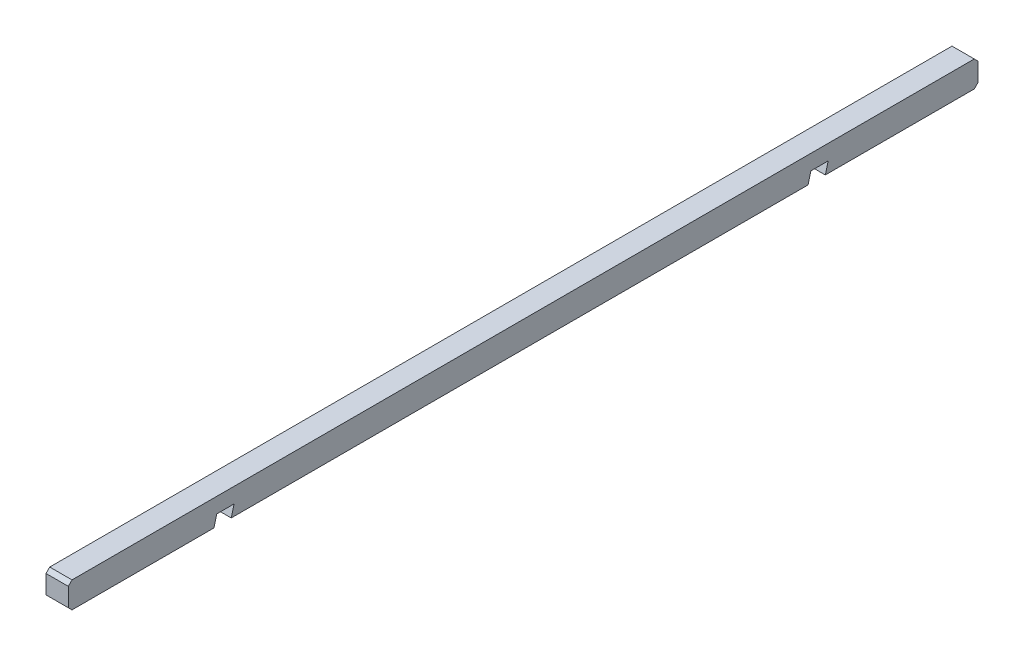
SolidWorks part; units mm, degrees
ref_plane "Front" through (0, 0, 0) normal (0, 0, 1) x (1, 0, 0)
ref_plane "Top" through (0, 0, 0) normal (0, 1, 0) x (1, 0, 0)
ref_plane "Right" through (0, 0, 0) normal (1, 0, 0) x (0, 0, -1)
sketch "Esquisse1" plane through (0, 0, 0) normal (0, 0, 1) x (1, 0, 0)
  line L1 (0, 0) -> (60, 0)
  line L2 (0, 0) -> (0, 70)
  line L3 (0, 70) -> (60, 70)
  line L4 (60, 0) -> (60, 70)
  dimension "D1" = 60
  dimension "D2" = 70
extrude "Boss.-Extru.1" add sketch "Esquisse1" along normal blind 2450
sketch "Esquisse2" plane through (0, 0, 0) normal (-1, 0, 0) x (0, 0, 1)
  line L0 (2057.7646, 0) -> (2050, 28.9778)
  line L1 (2450, 0) -> (0, 0) construction
  line L2 (2050, 28.9778) -> (2003.4126, 28.9778)
  line L3 (2003.4126, 28.9778) -> (2011.1771, 0)
  line L4 (2011.1771, 0) -> (2057.7646, 0)
  line L6 (2450, 70) -> (2450, 0) construction
  line L7 (457.7646, 0) -> (450, 28.9778)
  line L8 (450, 28.9778) -> (403.4126, 28.9778)
  line L9 (403.4126, 28.9778) -> (411.1771, 0)
  line L10 (411.1771, 0) -> (457.7646, 0)
  dimension "D1" = 75
  dimension "D2" = 30
  dimension "D3" = 45
  dimension "D4" = 400
  dimension "D6" = 1600
  dimension "D5" = 2
extrude "Enlèv. mat.-Extru.1" cut sketch "Esquisse2" against normal up to vertex (60 mm away) up to point (60, 0, 2450)
sketch "Esquisse3" plane through (0, 0, 0) normal (-1, 0, 0) x (0, 0, 1)
  line L0 (2450, 70) -> (3311.547, -1422.2432)
  line L1 (3311.547, -1422.2432) -> (3224.9445, -1472.2432)
  line L2 (3224.9445, -1472.2432) -> (2374.9445, 0)
  line L3 (2450, 0) -> (2057.7646, 0) construction
  line L6 (2374.9445, 0) -> (2450, 0)
  line L7 (2450, 70) -> (2450, 0) construction
  line L8 (2450, 0) -> (2450, 70)
  line L9 (2450, 70) -> (0, 70) construction
  dimension "D1" = 120
  dimension "D2" = 100
  dimension "D3" = 1700
chamfer "Chanfrein1" distance 10 angle 45 4 edges at (30, 70, 2450) (30, 0, 2450) (30, 0, 0) (30, 70, 0)
